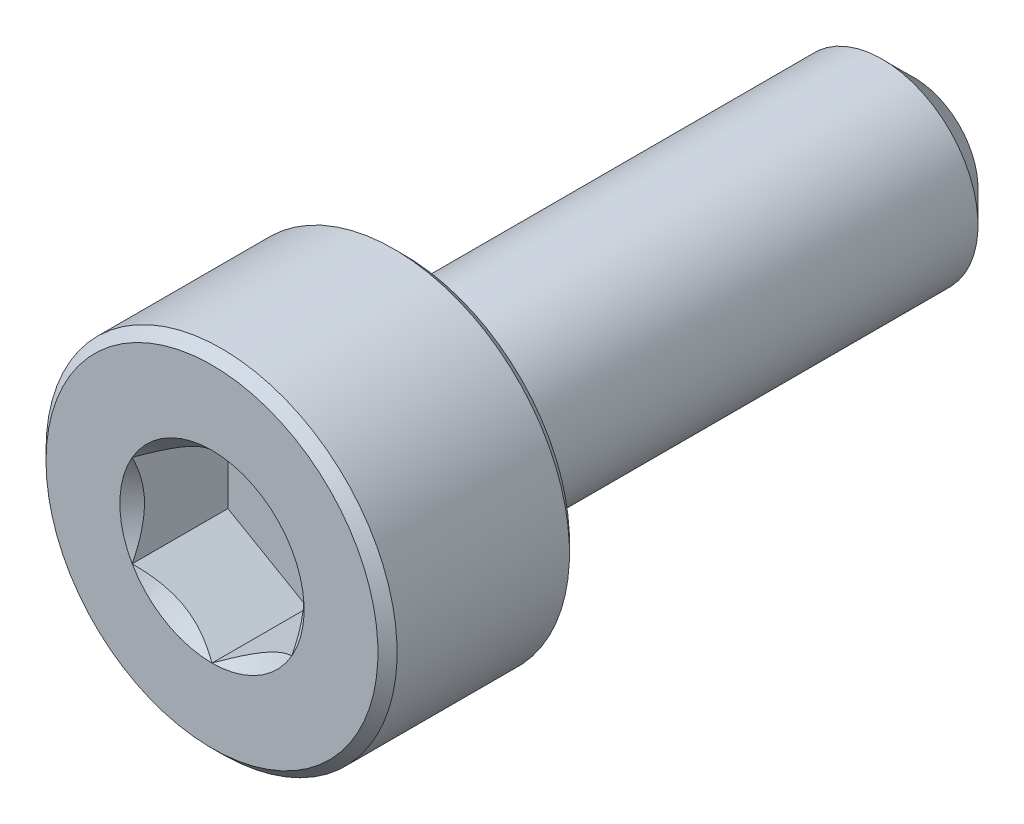
SolidWorks part; units mm, degrees
ref_plane "Front Plane" through (0, 0, 0) normal (0, 0, 1) x (1, 0, 0)
ref_plane "Top Plane" through (0, 0, 0) normal (0, 1, 0) x (1, 0, 0)
ref_plane "Right Plane" through (0, 0, 0) normal (1, 0, 0) x (0, 0, -1)
sketch "Sketch1" plane through (0, 0, 0) normal (1, 0, 0) x (0, 0, -1)
  line L0 (-5.5, 0) -> (5.5, 0) construction
  line L1 (5.5, 0) -> (5.5, 1) construction
  line L2 (5.5, 1) -> (5, 1.5) construction
  line L3 (5, 1.5) -> (-2.5, 1.5) construction
  line L5 (-2.5, 1.5) -> (-2.5, 2.75) construction
  line L6 (-2.5, 2.75) -> (-5.5, 2.75) construction
  line L7 (-5.5, 2.75) -> (-5.5, 0) construction
  line L8 (5.5, 1) -> (5.5, 1.5) construction
  line L9 (5.4688, 1.5541) -> (5.7188, 1.1211) construction
  line L10 (5.7188, 1.1211) -> (5.9688, 1.5541) construction
  line L11 (5.9688, 1.5541) -> (5.4688, 1.5541) construction
  line L12 (5.7188, 1.5541) -> (5.7188, 1.5) construction
  line L13 (5.7188, 1.1211) -> (5.7188, 1.1752) construction
  line L14 (5.6875, 1.1752) -> (5.75, 1.1752) construction
  line L15 (5.5, 1.5) -> (5.9375, 1.5) construction
  line L16 (5.4844, 1.5271) -> (5.9531, 1.5271) construction
  line L17 (5.5, 0) -> (5.5, -1.5) construction
  line L18 (-2.65, 2.75) -> (-2.5, 2.6) construction
  line L19 (-5.35, 2.75) -> (-5.5, 2.6) construction
  point P0 (-5.5, 1.25)
  point P3 (3.75, 1.5)
  point P4 (0, 0)
  point P22 (5.7188, 1.1752)
  point P24 (-2.5, 1.5)
  point P25 (5.7188, 1.5)
  point P28 (5.7188, 1.5271)
  point P29 (3.75, -1.5)
  point P31 (-4, 2.75)
  point P37 (-3.025, 2.75)
  point P38 (-5.275, 2.75)
  point P41 (-4, 0)
  dimension "head height" = 3
  dimension "D1" = 45
  dimension "Head Diameter" = 5.5
  dimension "Thread Size" = 3
  dimension "drive size" = 2.5
  dimension "Thread Pitch" = 0.5
  dimension "D2" = 0.0625
  dimension "D3" = 0.5
  dimension "D4" = 1.75
  dimension "D7" = 0.15
  dimension "D8" = 0.15
  dimension "D9" = 0.15
  dimension "D10" = 0.075
  dimension "D11" = 0.375
  dimension "length" = 8
  dimension "Drive Depth" = 1.5
sketch "Sketch2" plane through (0, 0, 0) normal (1, 0, 0) x (0, 0, -1)
  line L1 (-5.35, 2.75) -> (-2.65, 2.75)
  line L4 (5, 1.5) -> (5.5, 1)
  line L5 (5.5, 1) -> (5.5, 0)
  line L6 (-2.65, 2.75) -> (-2.5, 2.6) construction
  line L7 (5.5, 0) -> (-5.5, 0)
  line L8 (-5.35, 2.75) -> (-5.5, 2.6) construction
  line L9 (-2.65, 2.75) -> (-2.5, 2.6)
  line L10 (-5.35, 2.75) -> (-5.5, 2.6)
  line L11 (-5.5, 2.6) -> (-5.5, 0)
  line L12 (-2.5, 2.6) -> (-2.5, 1.5)
  line L13 (-2.5, 1.5) -> (5, 1.5)
revolve "Revolve1" add sketch "Sketch2" angle 360 about L7
sketch "Sketch3" plane through (0, 0, 5.5) normal (0, 0, 1) x (1, 0, 0)
  line L1 (0, 1.4434) -> (-1.25, 0.7217)
  line L2 (-1.25, 0.7217) -> (-1.25, -0.7217)
  line L3 (-1.25, -0.7217) -> (0, -1.4434)
  line L4 (0, -1.4434) -> (1.25, -0.7217)
  line L5 (1.25, -0.7217) -> (1.25, 0.7217)
  line L6 (1.25, 0.7217) -> (0, 1.4434)
  circle A0 centre (0, 0) radius 1.25 construction
  dimension "D1" = 2.5
extrude "Cut-Extrude1" cut sketch "Sketch3" against normal up to vertex (1.5 mm away) up to point (0, 0, 4)
sketch "Sketch4" plane through (0, 0, 5.5) normal (0, 0, 1) x (1, 0, 0)
  circle A0 centre (0, 0) radius 1.4434
extrude "Cut-Extrude2" cut sketch "Sketch4" against normal blind 0.5 draft 45
ref_plane "Plane1" [suppressed] through (0, 0, 2.5) normal (0, 0, 1) x (1, 0, 0)
split "Split1" [suppressed] bodies to split 106
sketch "Sketch6" [suppressed] plane through (0, 0, -5.5) normal (0, 0, -1) x (-1, 0, 0)
  circle A0 centre (0, 0) radius 1.5
curve "Helix/Spiral1" [suppressed] pitch 0.5 height 8.5 turns 17
sketch "Sketch7" [suppressed] plane through (0, 0, 0) normal (1, 0, 0) x (0, 0, -1)
  line L0 (5.4844, 1.5271) -> (5.9531, 1.5271)
  line L1 (5.9531, 1.5271) -> (5.75, 1.1752)
  line L2 (5.75, 1.1752) -> (5.6875, 1.1752)
  line L3 (5.6875, 1.1752) -> (5.4844, 1.5271)
sweep "Cut-Sweep1" [suppressed] cut profiles "Sketch7" path "Helix/Spiral1"
sketch "Sketch8" [suppressed] plane through (0, 0, 2.5) normal (0, 0, -1) x (-1, 0, 0)
  circle A0 centre (0, 0) radius 1.5
extrude "Boss-Extrude1" [suppressed] add sketch "Sketch8" along normal through all draft 45
ref_plane "Plane2" [suppressed] through (0, 0, 4) normal (0, 0, 1) x (1, 0, 0)
sketch "Sketch9" [suppressed] plane through (0, 0, 4) normal (0, 0, 1) x (1, 0, 0)
  line L0 (0, 2.6744) -> (0.072, 2.7491)
  line L1 (0, 2.6744) -> (-0.072, 2.7491)
  line L2 (0, 2.75) -> (0, 0) construction
  line L3 (-0.072, 2.7491) -> (0, 0) construction
  line L4 (0, 0) -> (0.072, 2.7491) construction
  arc A0 (0.072, 2.7491) -> (-0.072, 2.7491) centre (0, 0) ccw
  circle A1 centre (0, 0) radius 2.6744 construction
  dimension "D1" = 5.5
  dimension "D2" = 5.3487
  dimension "D3" = 3
extrude "Cut-Extrude4" [suppressed] cut sketch "Sketch9" against normal up to vertex and the other way up to vertex
pattern_circular "CirPattern2" [suppressed] count 96 over 360 about axis through (0, 0, 5.5) along (0, 0, -1) of bodies 113
equation "\"D2@Sketch1\" = \"Thread Pitch@Sketch1\" / 8"
equation "\"D3@Sketch1\" = \"Thread Pitch@Sketch1\""
equation "\"D3@Helix/Spiral1\" = \"length@Sketch1\" + \"Thread Pitch@Sketch1\""
equation "\"D4@Helix/Spiral1\" = \"Thread Pitch@Sketch1\""
equation "\"D4@Sketch1\" = \"Thread Pitch@Sketch1\" * 3.5"
equation "\"D7@Sketch1\"=\"head height@Sketch1\"*.05"
equation "\"D8@Sketch1\"=\"D7@Sketch1\""
equation "\"D9@Sketch1\"=\"D7@Sketch1\""
equation "\"D10@Sketch1\"=\"D7@Sketch1\"/2"
equation "\"D11@Sketch1\"=\"D10@Sketch1\"*5"
equation "\"D1@CirPattern2\"=( 360 / \"D3@Sketch9\" )*0.8"
equation "\"D1@Sketch3\" = \"drive size@Sketch1\""
equation "\"D2@Sketch9\"=\"Head Diameter@Sketch1\" * 0.9725"
